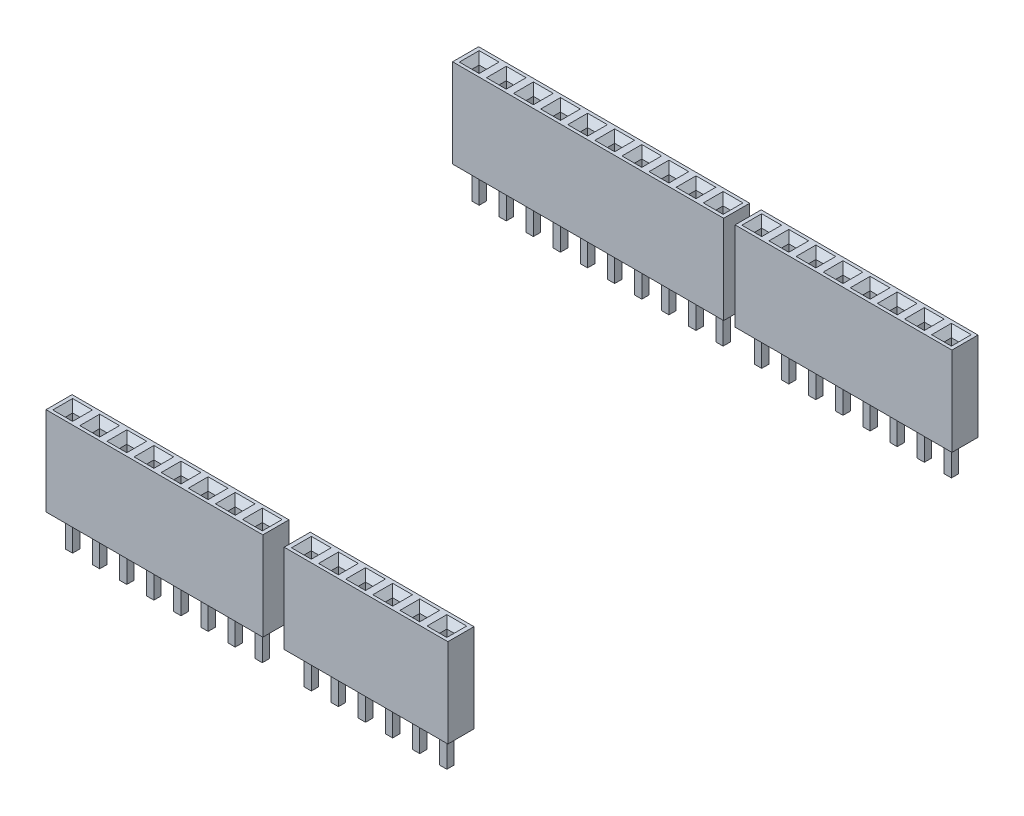
SolidWorks part; units mm, degrees
ref_plane "Plan de face" through (0, 0, 0) normal (0, 0, 1) x (1, 0, 0)
ref_plane "Plan de dessus" through (0, 0, 0) normal (0, 1, 0) x (1, 0, 0)
ref_plane "Plan de droite" through (0, 0, 0) normal (1, 0, 0) x (0, 0, -1)
sketch "Esquisse1" plane through (0, 0, 0) normal (0, 1, 0) x (1, 0, 0)
  line L0 (38.55, 0) -> (38.55, 55.8191) construction
  line L1 (0, 0) -> (20.8, 0)
  line L2 (0, 0) -> (0, 2.5)
  line L3 (0, 2.5) -> (20.8, 2.5)
  line L4 (20.8, 0) -> (20.8, 2.5)
  line L5 (22.85, 0) -> (38.55, 0)
  line L6 (22.85, 0) -> (22.85, 2.5)
  line L7 (22.85, 2.5) -> (38.55, 2.5)
  line L8 (38.55, 0) -> (38.55, 2.5)
  line L9 (38.5, 48.4) -> (17.7, 48.4)
  line L10 (38.5, 48.4) -> (38.5, 50.9)
  line L11 (38.5, 50.9) -> (17.7, 50.9)
  line L12 (17.7, 48.4) -> (17.7, 50.9)
  line L13 (16.6, 48.4) -> (-9.4, 48.4)
  line L14 (16.6, 48.4) -> (16.6, 50.9)
  line L15 (16.6, 50.9) -> (-9.4, 50.9)
  line L16 (-9.4, 48.4) -> (-9.4, 50.9)
  dimension "D1" = 20.8
  dimension "D2" = 2.5
  dimension "D3" = 15.7
  dimension "D4" = 2.5
  dimension "D5" = 2.05
  dimension "D6" = 45.9
  dimension "D7" = 20.8
  dimension "D8" = 2.5
  dimension "D9" = 2.5
  dimension "D10" = 1.1
  dimension "D11" = 26
  dimension "D12" = 0.05
extrude "Boss.-Extru.1" add sketch "Esquisse1" along normal blind 8.5
sketch "Esquisse2" plane through (0, 0, 0) normal (0, -1, 0) x (1, 0, 0)
  line L0 (0, -1.25) -> (0.95, -1.25) construction
  line L1 (0, -2.5) -> (0, 0) construction
  line L2 (20.8, 0) -> (20.8, -2.5) construction
  line L3 (22.85, -1.25) -> (38.55, -1.25) construction
  line L4 (22.85, -2.5) -> (22.85, 0) construction
  line L5 (38.55, 0) -> (38.55, -2.5) construction
  line L6 (-6.8, -49.65) -> (16.6, -49.65) construction
  line L8 (16.6, -48.4) -> (16.6, -50.9) construction
  line L9 (20.3, -49.65) -> (38.5, -49.65) construction
  line L11 (38.5, -48.4) -> (38.5, -50.9) construction
  line L12 (2.6, 0) -> (2.6, -2.5) construction
  line L13 (0, 0) -> (20.8, 0) construction
  line L14 (20.8, -2.5) -> (0, -2.5) construction
  line L15 (0.95, -1.25) -> (1.65, -1.25) construction
  line L16 (0.95, -1.6) -> (1.65, -1.6)
  line L17 (0.95, -1.6) -> (0.95, -0.9)
  line L18 (0.95, -0.9) -> (1.65, -0.9)
  line L19 (1.65, -1.6) -> (1.65, -0.9)
  line L20 (1.65, -1.25) -> (20.8, -1.25) construction
  line L21 (1.3, -0.9) -> (1.3, -1.6) construction
  line L22 (3.55, -1.6) -> (4.25, -1.6)
  line L23 (3.55, -1.6) -> (3.55, -0.9)
  line L24 (3.55, -0.9) -> (4.25, -0.9)
  line L25 (4.25, -1.6) -> (4.25, -0.9)
  line L26 (3.55, -1.25) -> (4.25, -1.25) construction
  line L27 (3.9, -0.9) -> (3.9, -1.6) construction
  line L28 (6.15, -1.6) -> (6.85, -1.6)
  line L29 (6.15, -1.6) -> (6.15, -0.9)
  line L30 (6.15, -0.9) -> (6.85, -0.9)
  line L31 (6.85, -1.6) -> (6.85, -0.9)
  line L32 (6.15, -1.25) -> (6.85, -1.25) construction
  line L33 (6.5, -0.9) -> (6.5, -1.6) construction
  line L34 (8.75, -1.6) -> (9.45, -1.6)
  line L35 (8.75, -1.6) -> (8.75, -0.9)
  line L36 (8.75, -0.9) -> (9.45, -0.9)
  line L37 (9.45, -1.6) -> (9.45, -0.9)
  line L38 (8.75, -1.25) -> (9.45, -1.25) construction
  line L39 (9.1, -0.9) -> (9.1, -1.6) construction
  line L40 (11.35, -1.6) -> (12.05, -1.6)
  line L41 (11.35, -1.6) -> (11.35, -0.9)
  line L42 (11.35, -0.9) -> (12.05, -0.9)
  line L43 (12.05, -1.6) -> (12.05, -0.9)
  line L44 (11.35, -1.25) -> (12.05, -1.25) construction
  line L45 (11.7, -0.9) -> (11.7, -1.6) construction
  line L46 (13.95, -1.6) -> (14.65, -1.6)
  line L47 (13.95, -1.6) -> (13.95, -0.9)
  line L48 (13.95, -0.9) -> (14.65, -0.9)
  line L49 (14.65, -1.6) -> (14.65, -0.9)
  line L50 (13.95, -1.25) -> (14.65, -1.25) construction
  line L51 (14.3, -0.9) -> (14.3, -1.6) construction
  line L52 (16.55, -1.6) -> (17.25, -1.6)
  line L53 (16.55, -1.6) -> (16.55, -0.9)
  line L54 (16.55, -0.9) -> (17.25, -0.9)
  line L55 (17.25, -1.6) -> (17.25, -0.9)
  line L56 (16.55, -1.25) -> (17.25, -1.25) construction
  line L57 (16.9, -0.9) -> (16.9, -1.6) construction
  line L58 (19.15, -1.6) -> (19.85, -1.6)
  line L59 (19.15, -1.6) -> (19.15, -0.9)
  line L60 (19.15, -0.9) -> (19.85, -0.9)
  line L61 (19.85, -1.6) -> (19.85, -0.9)
  line L62 (19.15, -1.25) -> (19.85, -1.25) construction
  line L63 (19.5, -0.9) -> (19.5, -1.6) construction
  line L64 (23.85, -1.6) -> (24.55, -1.6)
  line L65 (23.85, -1.6) -> (23.85, -0.9)
  line L66 (23.85, -0.9) -> (24.55, -0.9)
  line L67 (24.55, -1.6) -> (24.55, -0.9)
  line L68 (23.85, -1.25) -> (24.55, -1.25) construction
  line L69 (24.2, -0.9) -> (24.2, -1.6) construction
  line L70 (26.45, -1.6) -> (27.15, -1.6)
  line L71 (26.45, -1.6) -> (26.45, -0.9)
  line L72 (26.45, -0.9) -> (27.15, -0.9)
  line L73 (27.15, -1.6) -> (27.15, -0.9)
  line L74 (26.45, -1.25) -> (27.15, -1.25) construction
  line L75 (26.8, -0.9) -> (26.8, -1.6) construction
  line L76 (29.05, -1.6) -> (29.75, -1.6)
  line L77 (29.05, -1.6) -> (29.05, -0.9)
  line L78 (29.05, -0.9) -> (29.75, -0.9)
  line L79 (29.75, -1.6) -> (29.75, -0.9)
  line L80 (29.05, -1.25) -> (29.75, -1.25) construction
  line L81 (29.4, -0.9) -> (29.4, -1.6) construction
  line L82 (31.65, -1.6) -> (32.35, -1.6)
  line L83 (31.65, -1.6) -> (31.65, -0.9)
  line L84 (31.65, -0.9) -> (32.35, -0.9)
  line L85 (32.35, -1.6) -> (32.35, -0.9)
  line L86 (31.65, -1.25) -> (32.35, -1.25) construction
  line L87 (32, -0.9) -> (32, -1.6) construction
  line L88 (34.25, -1.6) -> (34.95, -1.6)
  line L89 (34.25, -1.6) -> (34.25, -0.9)
  line L90 (34.25, -0.9) -> (34.95, -0.9)
  line L91 (34.95, -1.6) -> (34.95, -0.9)
  line L92 (34.25, -1.25) -> (34.95, -1.25) construction
  line L93 (34.6, -0.9) -> (34.6, -1.6) construction
  line L94 (36.85, -1.6) -> (37.55, -1.6)
  line L95 (36.85, -1.6) -> (36.85, -0.9)
  line L96 (36.85, -0.9) -> (37.55, -0.9)
  line L97 (37.55, -1.6) -> (37.55, -0.9)
  line L98 (36.85, -1.25) -> (37.55, -1.25) construction
  line L99 (37.2, -0.9) -> (37.2, -1.6) construction
  line L100 (-6.8, -48.4) -> (-6.8, -50.9) construction
  line L101 (-9.4, -48.4) -> (16.6, -48.4) construction
  line L102 (16.6, -50.9) -> (-9.4, -50.9) construction
  line L103 (-6.8, -49.65) -> (-9.4, -49.65) construction
  line L104 (-9.4, -50.9) -> (-9.4, -48.4) construction
  line L105 (-8.1, -50) -> (-8.1, -49.3) construction
  line L106 (-8.45, -50) -> (-7.75, -50)
  line L107 (-8.45, -50) -> (-8.45, -49.3)
  line L108 (-8.45, -49.3) -> (-7.75, -49.3)
  line L109 (-7.75, -50) -> (-7.75, -49.3)
  line L110 (-5.85, -50) -> (-5.15, -50)
  line L111 (-5.85, -50) -> (-5.85, -49.3)
  line L112 (-5.85, -49.3) -> (-5.15, -49.3)
  line L113 (-5.15, -50) -> (-5.15, -49.3)
  line L114 (-5.5, -50) -> (-5.5, -49.3) construction
  line L115 (-3.25, -50) -> (-2.55, -50)
  line L116 (-3.25, -50) -> (-3.25, -49.3)
  line L117 (-3.25, -49.3) -> (-2.55, -49.3)
  line L118 (-2.55, -50) -> (-2.55, -49.3)
  line L119 (-2.9, -50) -> (-2.9, -49.3) construction
  line L120 (-0.65, -50) -> (0.05, -50)
  line L121 (-0.65, -50) -> (-0.65, -49.3)
  line L122 (-0.65, -49.3) -> (0.05, -49.3)
  line L123 (0.05, -50) -> (0.05, -49.3)
  line L124 (-0.3, -50) -> (-0.3, -49.3) construction
  line L125 (1.95, -50) -> (2.65, -50)
  line L126 (1.95, -50) -> (1.95, -49.3)
  line L127 (1.95, -49.3) -> (2.65, -49.3)
  line L128 (2.65, -50) -> (2.65, -49.3)
  line L129 (2.3, -50) -> (2.3, -49.3) construction
  line L130 (4.55, -50) -> (5.25, -50)
  line L131 (4.55, -50) -> (4.55, -49.3)
  line L132 (4.55, -49.3) -> (5.25, -49.3)
  line L133 (5.25, -50) -> (5.25, -49.3)
  line L134 (4.9, -50) -> (4.9, -49.3) construction
  line L135 (7.15, -50) -> (7.85, -50)
  line L136 (7.15, -50) -> (7.15, -49.3)
  line L137 (7.15, -49.3) -> (7.85, -49.3)
  line L138 (7.85, -50) -> (7.85, -49.3)
  line L139 (7.5, -50) -> (7.5, -49.3) construction
  line L140 (9.75, -50) -> (10.45, -50)
  line L141 (9.75, -50) -> (9.75, -49.3)
  line L142 (9.75, -49.3) -> (10.45, -49.3)
  line L143 (10.45, -50) -> (10.45, -49.3)
  line L144 (10.1, -50) -> (10.1, -49.3) construction
  line L145 (12.35, -50) -> (13.05, -50)
  line L146 (12.35, -50) -> (12.35, -49.3)
  line L147 (12.35, -49.3) -> (13.05, -49.3)
  line L148 (13.05, -50) -> (13.05, -49.3)
  line L149 (12.7, -50) -> (12.7, -49.3) construction
  line L150 (14.95, -50) -> (15.65, -50)
  line L151 (14.95, -50) -> (14.95, -49.3)
  line L152 (14.95, -49.3) -> (15.65, -49.3)
  line L153 (15.65, -50) -> (15.65, -49.3)
  line L154 (15.3, -50) -> (15.3, -49.3) construction
  line L155 (20.3, -48.4) -> (20.3, -50.9) construction
  line L156 (17.7, -48.4) -> (38.5, -48.4) construction
  line L157 (38.5, -50.9) -> (17.7, -50.9) construction
  line L158 (20.3, -49.65) -> (17.7, -49.65) construction
  line L159 (17.7, -50.9) -> (17.7, -48.4) construction
  line L160 (19, -50) -> (19, -49.3) construction
  line L161 (18.65, -50) -> (19.35, -50)
  line L162 (18.65, -50) -> (18.65, -49.3)
  line L163 (18.65, -49.3) -> (19.35, -49.3)
  line L164 (19.35, -50) -> (19.35, -49.3)
  line L165 (21.25, -50) -> (21.95, -50)
  line L166 (21.25, -50) -> (21.25, -49.3)
  line L167 (21.25, -49.3) -> (21.95, -49.3)
  line L168 (21.95, -50) -> (21.95, -49.3)
  line L169 (21.6, -50) -> (21.6, -49.3) construction
  line L170 (23.85, -50) -> (24.55, -50)
  line L171 (23.85, -50) -> (23.85, -49.3)
  line L172 (23.85, -49.3) -> (24.55, -49.3)
  line L173 (24.55, -50) -> (24.55, -49.3)
  line L174 (24.2, -50) -> (24.2, -49.3) construction
  line L175 (26.45, -50) -> (27.15, -50)
  line L176 (26.45, -50) -> (26.45, -49.3)
  line L177 (26.45, -49.3) -> (27.15, -49.3)
  line L178 (27.15, -50) -> (27.15, -49.3)
  line L179 (26.8, -50) -> (26.8, -49.3) construction
  line L180 (29.05, -50) -> (29.75, -50)
  line L181 (29.05, -50) -> (29.05, -49.3)
  line L182 (29.05, -49.3) -> (29.75, -49.3)
  line L183 (29.75, -50) -> (29.75, -49.3)
  line L184 (29.4, -50) -> (29.4, -49.3) construction
  line L185 (31.65, -50) -> (32.35, -50)
  line L186 (31.65, -50) -> (31.65, -49.3)
  line L187 (31.65, -49.3) -> (32.35, -49.3)
  line L188 (32.35, -50) -> (32.35, -49.3)
  line L189 (32, -50) -> (32, -49.3) construction
  line L190 (34.25, -50) -> (34.95, -50)
  line L191 (34.25, -50) -> (34.25, -49.3)
  line L192 (34.25, -49.3) -> (34.95, -49.3)
  line L193 (34.95, -50) -> (34.95, -49.3)
  line L194 (34.6, -50) -> (34.6, -49.3) construction
  line L195 (36.85, -50) -> (37.55, -50)
  line L196 (36.85, -50) -> (36.85, -49.3)
  line L197 (36.85, -49.3) -> (37.55, -49.3)
  line L198 (37.55, -50) -> (37.55, -49.3)
  line L199 (37.2, -50) -> (37.2, -49.3) construction
  point P12 (-8.1, -49.65)
  point P18 (19, -49.65)
  point P37 (1.3, -1.25)
  point P39 (1.3, -1.25)
  point P48 (3.9, -1.25)
  point P50 (3.9, -1.25)
  point P58 (6.5, -1.25)
  point P60 (6.5, -1.25)
  point P68 (9.1, -1.25)
  point P70 (9.1, -1.25)
  point P78 (11.7, -1.25)
  point P80 (11.7, -1.25)
  point P88 (14.3, -1.25)
  point P90 (14.3, -1.25)
  point P98 (16.9, -1.25)
  point P100 (16.9, -1.25)
  point P108 (19.5, -1.25)
  point P110 (19.5, -1.25)
  point P119 (24.2, -1.25)
  point P121 (24.2, -1.25)
  point P128 (26.8, -1.25)
  point P130 (26.8, -1.25)
  point P138 (29.4, -1.25)
  point P140 (29.4, -1.25)
  point P148 (32, -1.25)
  point P150 (32, -1.25)
  point P158 (34.6, -1.25)
  point P160 (34.6, -1.25)
  point P168 (37.2, -1.25)
  point P170 (37.2, -1.25)
  point P176 (-6.8, -49.65)
  point P185 (-8.1, -49.65)
  point P187 (-5.5, -49.65)
  point P194 (-5.5, -49.65)
  point P195 (-2.9, -49.65)
  point P202 (-2.9, -49.65)
  point P203 (-0.3, -49.65)
  point P210 (-0.3, -49.65)
  point P211 (2.3, -49.65)
  point P218 (2.3, -49.65)
  point P219 (4.9, -49.65)
  point P226 (4.9, -49.65)
  point P227 (7.5, -49.65)
  point P234 (7.5, -49.65)
  point P235 (10.1, -49.65)
  point P242 (10.1, -49.65)
  point P243 (12.7, -49.65)
  point P250 (12.7, -49.65)
  point P251 (15.3, -49.65)
  point P258 (15.3, -49.65)
  point P272 (19, -49.65)
  point P274 (21.6, -49.65)
  point P281 (21.6, -49.65)
  point P282 (24.2, -49.65)
  point P289 (24.2, -49.65)
  point P290 (26.8, -49.65)
  point P297 (26.8, -49.65)
  point P298 (29.4, -49.65)
  point P305 (29.4, -49.65)
  point P306 (32, -49.65)
  point P313 (32, -49.65)
  point P314 (34.6, -49.65)
  point P321 (34.6, -49.65)
  point P322 (37.2, -49.65)
  point P329 (37.2, -49.65)
  dimension "D1" = 2.6
  dimension "D2" = 0.7
  dimension "D6" = 2.6
  dimension "D7" = 0.7
  dimension "D9" = 2.6
  dimension "D10" = 0.7
  dimension "D12" = 1.35
  dimension "D3" = 8
  dimension "D4" = 2
  dimension "D5" = 6
  dimension "D8" = 10
  dimension "D11" = 8
extrude "Boss.-Extru.2" add sketch "Esquisse2" along normal blind 3.2
chamfer "Chanfrein1" distance 0.15 angle 45 32 edges at (19.5, -3.2, -0.9) (19.85, -3.2, -1.25) (19.5, -3.2, -1.6) (19.15, -3.2, -1.25) (16.9, -3.2, -0.9) (17.25, -3.2, -1.25) (16.9, -3.2, -1.6) (16.55, -3.2, -1.25) (14.3, -3.2, -0.9) (14.65, -3.2, -1.25) (14.3, -3.2, -1.6) (13.95, -3.2, -1.25) (11.7, -3.2, -0.9) (12.05, -3.2, -1.25) (11.7, -3.2, -1.6) (11.35, -3.2, -1.25) (9.1, -3.2, -0.9) (9.45, -3.2, -1.25) (9.1, -3.2, -1.6) (8.75, -3.2, -1.25) (6.5, -3.2, -0.9) (6.85, -3.2, -1.25) (6.5, -3.2, -1.6) (6.15, -3.2, -1.25) (3.9, -3.2, -0.9) (4.25, -3.2, -1.25) (3.9, -3.2, -1.6) (3.55, -3.2, -1.25) (1.3, -3.2, -0.9) (1.65, -3.2, -1.25) (1.3, -3.2, -1.6) (0.95, -3.2, -1.25)
chamfer "Chanfrein2" distance 0.15 angle 45 24 edges at (37.2, -3.2, -0.9) (37.55, -3.2, -1.25) (37.2, -3.2, -1.6) (36.85, -3.2, -1.25) (34.6, -3.2, -0.9) (34.95, -3.2, -1.25) (34.6, -3.2, -1.6) (34.25, -3.2, -1.25) (32, -3.2, -0.9) (32.35, -3.2, -1.25) (32, -3.2, -1.6) (31.65, -3.2, -1.25) (29.4, -3.2, -0.9) (29.75, -3.2, -1.25) (29.4, -3.2, -1.6) (29.05, -3.2, -1.25) (26.8, -3.2, -0.9) (27.15, -3.2, -1.25) (26.8, -3.2, -1.6) (26.45, -3.2, -1.25) (24.2, -3.2, -0.9) (24.55, -3.2, -1.25) (24.2, -3.2, -1.6) (23.85, -3.2, -1.25)
chamfer "Chanfrein3" distance 0.15 angle 45 40 edges at (15.3, -3.2, -49.3) (15.65, -3.2, -49.65) (15.3, -3.2, -50) (14.95, -3.2, -49.65) (12.7, -3.2, -49.3) (13.05, -3.2, -49.65) (12.7, -3.2, -50) (12.35, -3.2, -49.65) (10.1, -3.2, -49.3) (10.45, -3.2, -49.65) (10.1, -3.2, -50) (9.75, -3.2, -49.65) (7.5, -3.2, -49.3) (7.85, -3.2, -49.65) (7.5, -3.2, -50) (7.15, -3.2, -49.65) (4.9, -3.2, -49.3) (5.25, -3.2, -49.65) (4.9, -3.2, -50) (4.55, -3.2, -49.65) (2.3, -3.2, -49.3) (2.65, -3.2, -49.65) (2.3, -3.2, -50) (1.95, -3.2, -49.65) (-0.3, -3.2, -49.3) (0.05, -3.2, -49.65) (-0.3, -3.2, -50) (-0.65, -3.2, -49.65) (-2.9, -3.2, -49.3) (-2.55, -3.2, -49.65) (-2.9, -3.2, -50) (-3.25, -3.2, -49.65) (-5.5, -3.2, -49.3) (-5.15, -3.2, -49.65) (-5.5, -3.2, -50) (-5.85, -3.2, -49.65) (-8.1, -3.2, -49.3) (-7.75, -3.2, -49.65) (-8.1, -3.2, -50) (-8.45, -3.2, -49.65)
chamfer "Chanfrein4" distance 0.15 angle 45 32 edges at (19, -3.2, -49.3) (19.35, -3.2, -49.65) (19, -3.2, -50) (18.65, -3.2, -49.65) (37.2, -3.2, -49.3) (37.55, -3.2, -49.65) (37.2, -3.2, -50) (36.85, -3.2, -49.65) (34.6, -3.2, -49.3) (34.95, -3.2, -49.65) (34.6, -3.2, -50) (34.25, -3.2, -49.65) (32, -3.2, -49.3) (32.35, -3.2, -49.65) (32, -3.2, -50) (31.65, -3.2, -49.65) (29.4, -3.2, -49.3) (29.75, -3.2, -49.65) (29.4, -3.2, -50) (29.05, -3.2, -49.65) (26.8, -3.2, -49.3) (27.15, -3.2, -49.65) (26.8, -3.2, -50) (26.45, -3.2, -49.65) (24.2, -3.2, -49.3) (24.55, -3.2, -49.65) (24.2, -3.2, -50) (23.85, -3.2, -49.65) (21.6, -3.2, -49.3) (21.95, -3.2, -49.65) (21.6, -3.2, -50) (21.25, -3.2, -49.65)
sketch "Esquisse3" plane through (0, 8.5, 0) normal (0, 1, 0) x (1, 0, 0)
  line L4 (24.55, 50) -> (23.85, 50)
  line L5 (24.55, 49.3) -> (24.55, 50)
  line L6 (23.85, 49.3) -> (24.55, 49.3)
  line L7 (23.85, 50) -> (23.85, 49.3)
  line L8 (24.55, 50) -> (23.85, 50)
  line L9 (24.55, 49.3) -> (24.55, 50)
  line L10 (23.85, 49.3) -> (24.55, 49.3)
  line L11 (23.85, 50) -> (23.85, 49.3)
  line L12 (21.95, 50) -> (21.25, 50)
  line L13 (21.95, 49.3) -> (21.95, 50)
  line L14 (21.25, 49.3) -> (21.95, 49.3)
  line L15 (21.25, 50) -> (21.25, 49.3)
  line L16 (21.95, 50) -> (21.25, 50)
  line L17 (21.95, 49.3) -> (21.95, 50)
  line L18 (21.25, 49.3) -> (21.95, 49.3)
  line L19 (21.25, 50) -> (21.25, 49.3)
  line L20 (29.75, 50) -> (29.05, 50)
  line L21 (29.75, 49.3) -> (29.75, 50)
  line L22 (29.05, 49.3) -> (29.75, 49.3)
  line L23 (29.05, 50) -> (29.05, 49.3)
  line L24 (29.75, 50) -> (29.05, 50)
  line L25 (29.75, 49.3) -> (29.75, 50)
  line L26 (29.05, 49.3) -> (29.75, 49.3)
  line L27 (29.05, 50) -> (29.05, 49.3)
  line L28 (27.15, 50) -> (26.45, 50)
  line L29 (27.15, 49.3) -> (27.15, 50)
  line L30 (26.45, 49.3) -> (27.15, 49.3)
  line L31 (26.45, 50) -> (26.45, 49.3)
  line L32 (27.15, 50) -> (26.45, 50)
  line L33 (27.15, 49.3) -> (27.15, 50)
  line L34 (26.45, 49.3) -> (27.15, 49.3)
  line L35 (26.45, 50) -> (26.45, 49.3)
  line L36 (34.95, 50) -> (34.25, 50)
  line L37 (34.95, 49.3) -> (34.95, 50)
  line L38 (34.25, 49.3) -> (34.95, 49.3)
  line L39 (34.25, 50) -> (34.25, 49.3)
  line L40 (34.95, 50) -> (34.25, 50)
  line L41 (34.95, 49.3) -> (34.95, 50)
  line L42 (34.25, 49.3) -> (34.95, 49.3)
  line L43 (34.25, 50) -> (34.25, 49.3)
  line L44 (32.35, 50) -> (31.65, 50)
  line L45 (32.35, 49.3) -> (32.35, 50)
  line L46 (31.65, 49.3) -> (32.35, 49.3)
  line L47 (31.65, 50) -> (31.65, 49.3)
  line L48 (32.35, 50) -> (31.65, 50)
  line L49 (32.35, 49.3) -> (32.35, 50)
  line L50 (31.65, 49.3) -> (32.35, 49.3)
  line L51 (31.65, 50) -> (31.65, 49.3)
  line L52 (4.25, 1.6) -> (3.55, 1.6)
  line L53 (4.25, 0.9) -> (4.25, 1.6)
  line L54 (3.55, 0.9) -> (4.25, 0.9)
  line L55 (3.55, 1.6) -> (3.55, 0.9)
  line L56 (4.25, 1.6) -> (3.55, 1.6)
  line L57 (4.25, 0.9) -> (4.25, 1.6)
  line L58 (3.55, 0.9) -> (4.25, 0.9)
  line L59 (3.55, 1.6) -> (3.55, 0.9)
  line L60 (1.65, 1.6) -> (0.95, 1.6)
  line L61 (0.95, 1.6) -> (0.95, 0.9)
  line L62 (0.95, 0.9) -> (1.65, 0.9)
  line L63 (1.65, 0.9) -> (1.65, 1.6)
  line L64 (1.65, 1.6) -> (0.95, 1.6)
  line L65 (0.95, 1.6) -> (0.95, 0.9)
  line L66 (0.95, 0.9) -> (1.65, 0.9)
  line L67 (1.65, 0.9) -> (1.65, 1.6)
  line L68 (37.55, 50) -> (36.85, 50)
  line L69 (37.55, 49.3) -> (37.55, 50)
  line L70 (36.85, 49.3) -> (37.55, 49.3)
  line L71 (36.85, 50) -> (36.85, 49.3)
  line L72 (37.55, 50) -> (36.85, 50)
  line L73 (37.55, 49.3) -> (37.55, 50)
  line L74 (36.85, 49.3) -> (37.55, 49.3)
  line L75 (36.85, 50) -> (36.85, 49.3)
  line L76 (6.85, 1.6) -> (6.15, 1.6)
  line L77 (6.85, 0.9) -> (6.85, 1.6)
  line L78 (6.15, 0.9) -> (6.85, 0.9)
  line L79 (6.15, 1.6) -> (6.15, 0.9)
  line L80 (6.85, 1.6) -> (6.15, 1.6)
  line L81 (6.85, 0.9) -> (6.85, 1.6)
  line L82 (6.15, 0.9) -> (6.85, 0.9)
  line L83 (6.15, 1.6) -> (6.15, 0.9)
  line L84 (12.05, 1.6) -> (11.35, 1.6)
  line L85 (12.05, 0.9) -> (12.05, 1.6)
  line L86 (11.35, 0.9) -> (12.05, 0.9)
  line L87 (11.35, 1.6) -> (11.35, 0.9)
  line L88 (12.05, 1.6) -> (11.35, 1.6)
  line L89 (12.05, 0.9) -> (12.05, 1.6)
  line L90 (11.35, 0.9) -> (12.05, 0.9)
  line L91 (11.35, 1.6) -> (11.35, 0.9)
  line L92 (9.45, 1.6) -> (8.75, 1.6)
  line L93 (8.75, 1.6) -> (8.75, 0.9)
  line L94 (8.75, 0.9) -> (9.45, 0.9)
  line L95 (9.45, 0.9) -> (9.45, 1.6)
  line L96 (9.45, 1.6) -> (8.75, 1.6)
  line L97 (8.75, 1.6) -> (8.75, 0.9)
  line L98 (8.75, 0.9) -> (9.45, 0.9)
  line L99 (9.45, 0.9) -> (9.45, 1.6)
  line L100 (17.25, 1.6) -> (16.55, 1.6)
  line L101 (17.25, 0.9) -> (17.25, 1.6)
  line L102 (16.55, 0.9) -> (17.25, 0.9)
  line L103 (16.55, 1.6) -> (16.55, 0.9)
  line L104 (17.25, 1.6) -> (16.55, 1.6)
  line L105 (17.25, 0.9) -> (17.25, 1.6)
  line L106 (16.55, 0.9) -> (17.25, 0.9)
  line L107 (16.55, 1.6) -> (16.55, 0.9)
  line L108 (14.65, 1.6) -> (13.95, 1.6)
  line L109 (14.65, 0.9) -> (14.65, 1.6)
  line L110 (13.95, 0.9) -> (14.65, 0.9)
  line L111 (13.95, 1.6) -> (13.95, 0.9)
  line L112 (14.65, 1.6) -> (13.95, 1.6)
  line L113 (14.65, 0.9) -> (14.65, 1.6)
  line L114 (13.95, 0.9) -> (14.65, 0.9)
  line L115 (13.95, 1.6) -> (13.95, 0.9)
  line L116 (19.85, 1.6) -> (19.15, 1.6)
  line L117 (19.85, 0.9) -> (19.85, 1.6)
  line L118 (19.15, 0.9) -> (19.85, 0.9)
  line L119 (19.15, 1.6) -> (19.15, 0.9)
  line L120 (19.85, 1.6) -> (19.15, 1.6)
  line L121 (19.85, 0.9) -> (19.85, 1.6)
  line L122 (19.15, 0.9) -> (19.85, 0.9)
  line L123 (19.15, 1.6) -> (19.15, 0.9)
  line L124 (27.15, 1.6) -> (26.45, 1.6)
  line L125 (26.45, 1.6) -> (26.45, 0.9)
  line L126 (26.45, 0.9) -> (27.15, 0.9)
  line L127 (27.15, 0.9) -> (27.15, 1.6)
  line L128 (27.15, 1.6) -> (26.45, 1.6)
  line L129 (26.45, 1.6) -> (26.45, 0.9)
  line L130 (26.45, 0.9) -> (27.15, 0.9)
  line L131 (27.15, 0.9) -> (27.15, 1.6)
  line L132 (24.55, 1.6) -> (23.85, 1.6)
  line L133 (24.55, 0.9) -> (24.55, 1.6)
  line L134 (23.85, 0.9) -> (24.55, 0.9)
  line L135 (23.85, 1.6) -> (23.85, 0.9)
  line L136 (24.55, 1.6) -> (23.85, 1.6)
  line L137 (24.55, 0.9) -> (24.55, 1.6)
  line L138 (23.85, 0.9) -> (24.55, 0.9)
  line L139 (23.85, 1.6) -> (23.85, 0.9)
  line L140 (29.75, 1.6) -> (29.05, 1.6)
  line L141 (29.75, 0.9) -> (29.75, 1.6)
  line L142 (29.05, 0.9) -> (29.75, 0.9)
  line L143 (29.05, 1.6) -> (29.05, 0.9)
  line L144 (29.75, 1.6) -> (29.05, 1.6)
  line L145 (29.75, 0.9) -> (29.75, 1.6)
  line L146 (29.05, 0.9) -> (29.75, 0.9)
  line L147 (29.05, 1.6) -> (29.05, 0.9)
  line L148 (34.95, 1.6) -> (34.25, 1.6)
  line L149 (34.95, 0.9) -> (34.95, 1.6)
  line L150 (34.25, 0.9) -> (34.95, 0.9)
  line L151 (34.25, 1.6) -> (34.25, 0.9)
  line L152 (34.95, 1.6) -> (34.25, 1.6)
  line L153 (34.95, 0.9) -> (34.95, 1.6)
  line L154 (34.25, 0.9) -> (34.95, 0.9)
  line L155 (34.25, 1.6) -> (34.25, 0.9)
  line L156 (32.35, 1.6) -> (31.65, 1.6)
  line L157 (31.65, 1.6) -> (31.65, 0.9)
  line L158 (31.65, 0.9) -> (32.35, 0.9)
  line L159 (32.35, 0.9) -> (32.35, 1.6)
  line L160 (32.35, 1.6) -> (31.65, 1.6)
  line L161 (31.65, 1.6) -> (31.65, 0.9)
  line L162 (31.65, 0.9) -> (32.35, 0.9)
  line L163 (32.35, 0.9) -> (32.35, 1.6)
  line L164 (37.55, 1.6) -> (36.85, 1.6)
  line L165 (37.55, 0.9) -> (37.55, 1.6)
  line L166 (36.85, 0.9) -> (37.55, 0.9)
  line L167 (36.85, 1.6) -> (36.85, 0.9)
  line L168 (37.55, 1.6) -> (36.85, 1.6)
  line L169 (37.55, 0.9) -> (37.55, 1.6)
  line L170 (36.85, 0.9) -> (37.55, 0.9)
  line L171 (36.85, 1.6) -> (36.85, 0.9)
  line L172 (-5.15, 50) -> (-5.85, 50)
  line L173 (-5.15, 49.3) -> (-5.15, 50)
  line L174 (-5.85, 49.3) -> (-5.15, 49.3)
  line L175 (-5.85, 50) -> (-5.85, 49.3)
  line L176 (-5.15, 50) -> (-5.85, 50)
  line L177 (-5.15, 49.3) -> (-5.15, 50)
  line L178 (-5.85, 49.3) -> (-5.15, 49.3)
  line L179 (-5.85, 50) -> (-5.85, 49.3)
  line L180 (-7.75, 50) -> (-8.45, 50)
  line L181 (-7.75, 49.3) -> (-7.75, 50)
  line L182 (-8.45, 49.3) -> (-7.75, 49.3)
  line L183 (-8.45, 50) -> (-8.45, 49.3)
  line L184 (-7.75, 50) -> (-8.45, 50)
  line L185 (-7.75, 49.3) -> (-7.75, 50)
  line L186 (-8.45, 49.3) -> (-7.75, 49.3)
  line L187 (-8.45, 50) -> (-8.45, 49.3)
  line L188 (0.05, 50) -> (-0.65, 50)
  line L189 (0.05, 49.3) -> (0.05, 50)
  line L190 (-0.65, 49.3) -> (0.05, 49.3)
  line L191 (-0.65, 50) -> (-0.65, 49.3)
  line L192 (0.05, 50) -> (-0.65, 50)
  line L193 (0.05, 49.3) -> (0.05, 50)
  line L194 (-0.65, 49.3) -> (0.05, 49.3)
  line L195 (-0.65, 50) -> (-0.65, 49.3)
  line L196 (-2.55, 50) -> (-3.25, 50)
  line L197 (-2.55, 49.3) -> (-2.55, 50)
  line L198 (-3.25, 49.3) -> (-2.55, 49.3)
  line L199 (-3.25, 50) -> (-3.25, 49.3)
  line L200 (-2.55, 50) -> (-3.25, 50)
  line L201 (-2.55, 49.3) -> (-2.55, 50)
  line L202 (-3.25, 49.3) -> (-2.55, 49.3)
  line L203 (-3.25, 50) -> (-3.25, 49.3)
  line L204 (5.25, 50) -> (4.55, 50)
  line L205 (5.25, 49.3) -> (5.25, 50)
  line L206 (4.55, 49.3) -> (5.25, 49.3)
  line L207 (4.55, 50) -> (4.55, 49.3)
  line L208 (5.25, 50) -> (4.55, 50)
  line L209 (5.25, 49.3) -> (5.25, 50)
  line L210 (4.55, 49.3) -> (5.25, 49.3)
  line L211 (4.55, 50) -> (4.55, 49.3)
  line L212 (2.65, 50) -> (1.95, 50)
  line L213 (2.65, 49.3) -> (2.65, 50)
  line L214 (1.95, 49.3) -> (2.65, 49.3)
  line L215 (1.95, 50) -> (1.95, 49.3)
  line L216 (2.65, 50) -> (1.95, 50)
  line L217 (2.65, 49.3) -> (2.65, 50)
  line L218 (1.95, 49.3) -> (2.65, 49.3)
  line L219 (1.95, 50) -> (1.95, 49.3)
  line L220 (10.45, 50) -> (9.75, 50)
  line L221 (10.45, 49.3) -> (10.45, 50)
  line L222 (9.75, 49.3) -> (10.45, 49.3)
  line L223 (9.75, 50) -> (9.75, 49.3)
  line L224 (10.45, 50) -> (9.75, 50)
  line L225 (10.45, 49.3) -> (10.45, 50)
  line L226 (9.75, 49.3) -> (10.45, 49.3)
  line L227 (9.75, 50) -> (9.75, 49.3)
  line L228 (7.85, 50) -> (7.15, 50)
  line L229 (7.85, 49.3) -> (7.85, 50)
  line L230 (7.15, 49.3) -> (7.85, 49.3)
  line L231 (7.15, 50) -> (7.15, 49.3)
  line L232 (7.85, 50) -> (7.15, 50)
  line L233 (7.85, 49.3) -> (7.85, 50)
  line L234 (7.15, 49.3) -> (7.85, 49.3)
  line L235 (7.15, 50) -> (7.15, 49.3)
  line L236 (15.65, 50) -> (14.95, 50)
  line L237 (15.65, 49.3) -> (15.65, 50)
  line L238 (14.95, 49.3) -> (15.65, 49.3)
  line L239 (14.95, 50) -> (14.95, 49.3)
  line L240 (15.65, 50) -> (14.95, 50)
  line L241 (15.65, 49.3) -> (15.65, 50)
  line L242 (14.95, 49.3) -> (15.65, 49.3)
  line L243 (14.95, 50) -> (14.95, 49.3)
  line L244 (13.05, 50) -> (12.35, 50)
  line L245 (13.05, 49.3) -> (13.05, 50)
  line L246 (12.35, 49.3) -> (13.05, 49.3)
  line L247 (12.35, 50) -> (12.35, 49.3)
  line L248 (13.05, 50) -> (12.35, 50)
  line L249 (13.05, 49.3) -> (13.05, 50)
  line L250 (12.35, 49.3) -> (13.05, 49.3)
  line L251 (12.35, 50) -> (12.35, 49.3)
  line L252 (19.35, 50) -> (18.65, 50)
  line L253 (19.35, 49.3) -> (19.35, 50)
  line L254 (18.65, 49.3) -> (19.35, 49.3)
  line L255 (18.65, 50) -> (18.65, 49.3)
  line L256 (19.35, 50) -> (18.65, 50)
  line L257 (19.35, 49.3) -> (19.35, 50)
  line L258 (18.65, 49.3) -> (19.35, 49.3)
  line L259 (18.65, 50) -> (18.65, 49.3)
  dimension "D1" = 0
  dimension "D2" = 0
  dimension "D3" = 0
  dimension "D4" = 0
  dimension "D5" = 0
  dimension "D6" = 0
  dimension "D7" = 0
  dimension "D8" = 0
  dimension "D9" = 0
  dimension "D10" = 0
  dimension "D11" = 0
  dimension "D12" = 0
  dimension "D13" = 0
  dimension "D14" = 0
  dimension "D15" = 0
  dimension "D16" = 0
  dimension "D17" = 0
  dimension "D18" = 0
  dimension "D19" = 0
  dimension "D20" = 0
  dimension "D21" = 0
  dimension "D22" = 0
  dimension "D23" = 0
  dimension "D24" = 0
  dimension "D25" = 0
  dimension "D26" = 0
  dimension "D27" = 0
  dimension "D28" = 0
  dimension "D29" = 0
  dimension "D30" = 0
  dimension "D31" = 0
  dimension "D32" = 0
extrude "Enlèv. mat.-Extru.1" cut sketch "Esquisse3" against normal blind 7
chamfer "Chanfrein5" distance 0.6 angle 45 40 edges at (-8.1, 8.5, -49.3) (-8.45, 8.5, -49.65) (-8.1, 8.5, -50) (-7.75, 8.5, -49.65) (15.3, 8.5, -49.3) (15.65, 8.5, -49.65) (15.3, 8.5, -50) (14.95, 8.5, -49.65) (12.7, 8.5, -49.3) (13.05, 8.5, -49.65) (12.7, 8.5, -50) (12.35, 8.5, -49.65) (10.1, 8.5, -49.3) (10.45, 8.5, -49.65) (10.1, 8.5, -50) (9.75, 8.5, -49.65) (7.5, 8.5, -49.3) (7.85, 8.5, -49.65) (7.5, 8.5, -50) (7.15, 8.5, -49.65) (4.9, 8.5, -49.3) (5.25, 8.5, -49.65) (4.9, 8.5, -50) (4.55, 8.5, -49.65) (2.3, 8.5, -49.3) (2.65, 8.5, -49.65) (2.3, 8.5, -50) (1.95, 8.5, -49.65) (-0.3, 8.5, -49.3) (0.05, 8.5, -49.65) (-0.3, 8.5, -50) (-0.65, 8.5, -49.65) (-2.9, 8.5, -49.3) (-2.55, 8.5, -49.65) (-2.9, 8.5, -50) (-3.25, 8.5, -49.65) (-5.5, 8.5, -49.3) (-5.15, 8.5, -49.65) (-5.5, 8.5, -50) (-5.85, 8.5, -49.65)
chamfer "Chanfrein6" distance 0.6 angle 45 32 edges at (37.2, 8.5, -49.3) (37.55, 8.5, -49.65) (37.2, 8.5, -50) (36.85, 8.5, -49.65) (34.6, 8.5, -49.3) (34.95, 8.5, -49.65) (34.6, 8.5, -50) (34.25, 8.5, -49.65) (32, 8.5, -49.3) (32.35, 8.5, -49.65) (32, 8.5, -50) (31.65, 8.5, -49.65) (29.4, 8.5, -49.3) (29.75, 8.5, -49.65) (29.4, 8.5, -50) (29.05, 8.5, -49.65) (26.8, 8.5, -49.3) (27.15, 8.5, -49.65) (26.8, 8.5, -50) (26.45, 8.5, -49.65) (24.2, 8.5, -49.3) (24.55, 8.5, -49.65) (24.2, 8.5, -50) (23.85, 8.5, -49.65) (21.6, 8.5, -49.3) (21.95, 8.5, -49.65) (21.6, 8.5, -50) (21.25, 8.5, -49.65) (19, 8.5, -49.3) (19.35, 8.5, -49.65) (19, 8.5, -50) (18.65, 8.5, -49.65)
chamfer "Chanfrein7" distance 0.6 angle 45 24 edges at (37.55, 8.5, -1.25) (37.2, 8.5, -1.6) (36.85, 8.5, -1.25) (37.2, 8.5, -0.9) (34.95, 8.5, -1.25) (34.6, 8.5, -1.6) (34.25, 8.5, -1.25) (34.6, 8.5, -0.9) (32.35, 8.5, -1.25) (32, 8.5, -1.6) (31.65, 8.5, -1.25) (32, 8.5, -0.9) (29.75, 8.5, -1.25) (29.4, 8.5, -1.6) (29.05, 8.5, -1.25) (29.4, 8.5, -0.9) (27.15, 8.5, -1.25) (26.8, 8.5, -1.6) (26.45, 8.5, -1.25) (26.8, 8.5, -0.9) (24.55, 8.5, -1.25) (24.2, 8.5, -1.6) (23.85, 8.5, -1.25) (24.2, 8.5, -0.9)
chamfer "Chanfrein8" distance 0.6 angle 45 32 edges at (1.65, 8.5, -1.25) (1.3, 8.5, -1.6) (0.95, 8.5, -1.25) (1.3, 8.5, -0.9) (4.25, 8.5, -1.25) (3.9, 8.5, -1.6) (3.55, 8.5, -1.25) (3.9, 8.5, -0.9) (6.85, 8.5, -1.25) (6.5, 8.5, -1.6) (6.15, 8.5, -1.25) (6.5, 8.5, -0.9) (9.45, 8.5, -1.25) (9.1, 8.5, -1.6) (8.75, 8.5, -1.25) (9.1, 8.5, -0.9) (12.05, 8.5, -1.25) (11.7, 8.5, -1.6) (11.35, 8.5, -1.25) (11.7, 8.5, -0.9) (14.65, 8.5, -1.25) (14.3, 8.5, -1.6) (13.95, 8.5, -1.25) (14.3, 8.5, -0.9) (17.25, 8.5, -1.25) (16.9, 8.5, -1.6) (16.55, 8.5, -1.25) (16.9, 8.5, -0.9) (19.85, 8.5, -1.25) (19.5, 8.5, -1.6) (19.15, 8.5, -1.25) (19.5, 8.5, -0.9)
